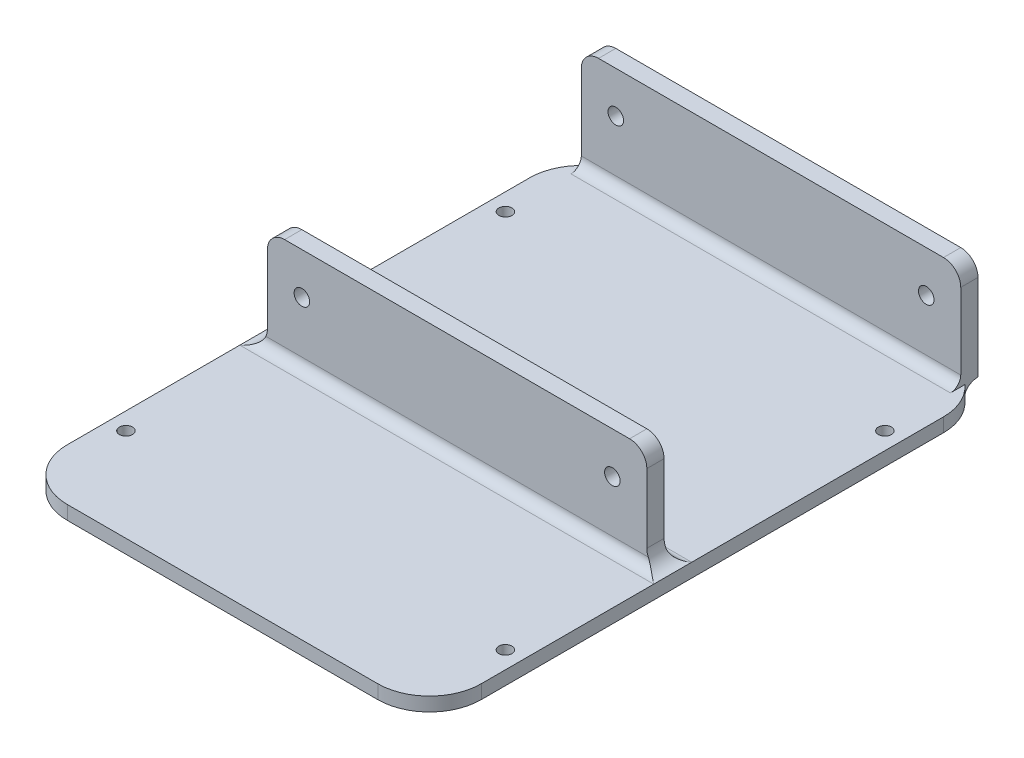
SolidWorks part; units mm, degrees
ref_plane "Спереди" through (0, 0, 0) normal (0, 0, 1) x (1, 0, 0)
ref_plane "Сверху" through (0, 0, 0) normal (0, 1, 0) x (1, 0, 0)
ref_plane "Справа" through (0, 0, 0) normal (1, 0, 0) x (0, 0, -1)
sketch "Эскиз1" plane through (0, 0, 0) normal (0, 1, 0) x (1, 0, 0)
  line L1 (-60, -82) -> (60, -82)
  line L2 (-60, -82) -> (-60, 82)
  line L3 (-60, 82) -> (60, 82)
  line L4 (60, -82) -> (60, 82)
  line L5 (0, 82) -> (0, -82) construction
  line L6 (-60, 0) -> (60, 0) construction
  line L7 (-55, -55) -> (55, -55) construction
  line L8 (-55, -55) -> (-55, 55) construction
  line L9 (-55, 55) -> (55, 55) construction
  line L10 (55, -55) -> (55, 55) construction
  line L11 (0, 55) -> (0, -55) construction
  line L12 (-55, 0) -> (55, 0) construction
  circle A0 centre (-55, 55) radius 1.9
  circle A1 centre (55, 55) radius 1.9
  circle A2 centre (55, -55) radius 1.9
  circle A3 centre (-55, -55) radius 1.9
  point P0 (0, 0)
  point P4 (0, 0)
  dimension "D5" = 3.8
  dimension "D1" = 120
  dimension "D2" = 164
  dimension "D3" = 110
  dimension "D4" = 110
extrude "Бобышка-Вытянуть1" add sketch "Эскиз1" along normal blind 4
fillet "Скругление1" radius 15 4 edges at (-60, 2, 82) (-60, 2, -82) (60, 2, -82) (60, 2, 82)
sketch "Эскиз2" plane through (0, 4, 0) normal (0, 1, 0) x (1, 0, 0)
  line L0 (45, 82) -> (-45, 82) construction
  line L1 (-55, 77) -> (55, 77)
  line L2 (-55, 77) -> (-55, 82)
  line L3 (-55, 82) -> (55, 82)
  line L4 (55, 77) -> (55, 82)
  line L5 (0, 82) -> (0, 77) construction
  line L6 (-55, 79.5) -> (55, 79.5) construction
  line L7 (-68.7864, 34) -> (83.8725, 34) construction
  line L8 (-55, -14) -> (55, -14)
  line L9 (55, -9) -> (55, -14)
  line L10 (-55, -9) -> (55, -9)
  line L11 (-55, -9) -> (-55, -14)
  point P0 (0, 79.5)
  dimension "D1" = 5
  dimension "D2" = 110
  dimension "D3" = 48
extrude "Бобышка-Вытянуть2" add sketch "Эскиз2" along normal blind 30
sketch "Эскиз3" plane through (0, 0, -82) normal (0, 0, 1) x (1, 0, 0)
  line L0 (0, 0) -> (0, 47.2629) construction
  line L1 (-61.1744, 22) -> (76.1206, 22) construction
  line L2 (-55, 34) -> (55, 34) construction
  circle A0 centre (-45, 22) radius 2.25
  circle A1 centre (45, 22) radius 2.25
  dimension "D2" = 4.5
  dimension "D3" = 45
  dimension "D1" = 12
extrude "Вырез-Вытянуть1" cut sketch "Эскиз3" along normal up to surface (96 mm away) up to face at (0, 19, 14)
fillet "Скругление2" radius 5 6 edges at (-55, 34, -79.5) (-55, 4, 11.5) (-55, 34, 11.5) (55, 4, 11.5) (55, 34, 11.5) (55, 34, -79.5)
fillet "Скругление3" radius 3 3 edges at (0, 4, -77) (0, 4, 14) (0, 4, 9)
fillet "Скругление4" radius 3 2 edges at (-50.3523, 4, -81.0126) (50.3523, 4, -81.0126)
